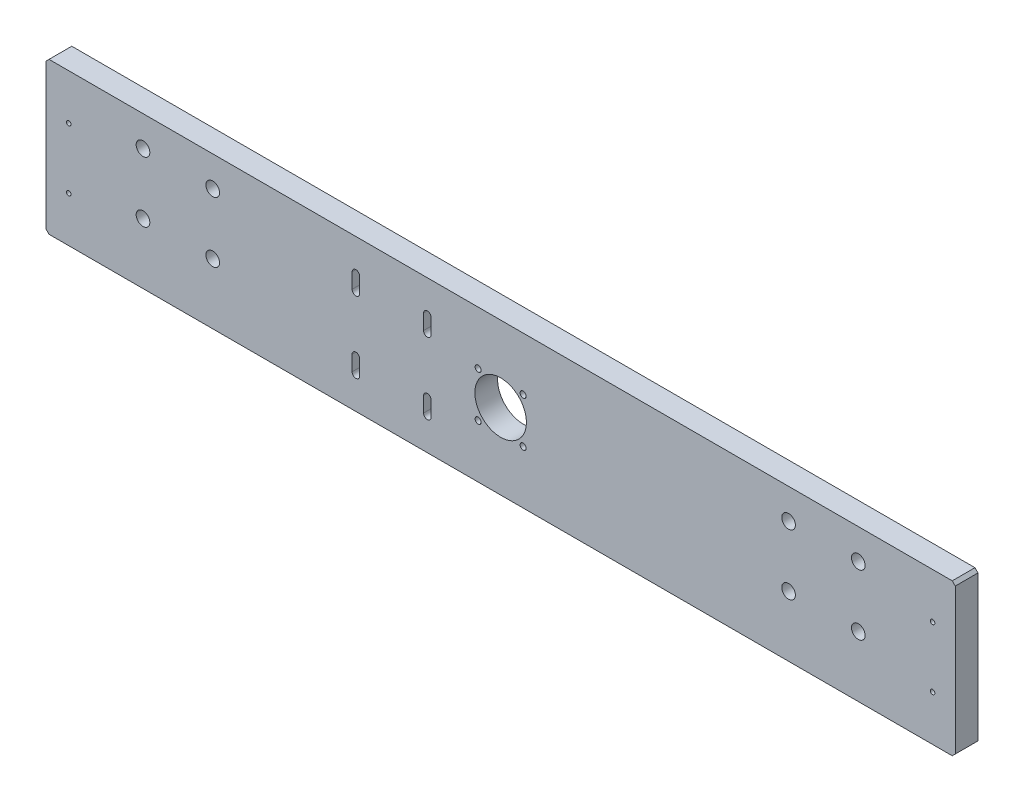
SolidWorks part; units mm, degrees
ref_plane "Piano frontale" through (0, 0, 0) normal (0, 0, 1) x (1, 0, 0)
ref_plane "Piano superiore" through (0, 0, 0) normal (0, 1, 0) x (1, 0, 0)
ref_plane "Piano destro" through (0, 0, 0) normal (1, 0, 0) x (0, 0, -1)
sketch "Schizzo1" plane through (0, 0, 0) normal (0, 0, 1) x (1, 0, 0)
  line L0 (300, 100) -> (300, 0) construction
  line L1 (2, 0) -> (598, 0)
  line L2 (0, 2) -> (0, 98)
  line L3 (2, 100) -> (598, 100)
  line L4 (600, 2) -> (600, 98)
  line L5 (87, 100) -> (87, 0) construction
  line L7 (300, 50) -> (318.5099, 50) construction
  line L9 (300, 50) -> (280.51, 69.49) construction
  line L21 (0, 98) -> (2, 100)
  line L22 (2, 0) -> (0, 2)
  line L23 (598, 0) -> (600, 2)
  line L24 (598, 100) -> (600, 98)
  circle A0 centre (300, 50) radius 17
  circle A1 centre (300, 50) radius 21 construction
  circle A2 centre (314.8492, 64.8492) radius 2
  circle A3 centre (314.8492, 35.1508) radius 2
  circle A4 centre (285.1508, 35.1508) radius 2
  circle A5 centre (536, 40) radius 4.5
  circle A6 centre (536, 80) radius 4.5
  circle A7 centre (490, 40) radius 4.5
  circle A8 centre (490, 80) radius 4.5
  circle A9 centre (585, 70) radius 1.5
  circle A10 centre (585, 30) radius 1.5
  circle A11 centre (15, 30) radius 1.5
  circle A13 centre (285.1508, 64.8492) radius 2
  circle A18 centre (15, 70) radius 1.5
  circle A29 centre (110, 80) radius 4.5
  circle A30 centre (110, 40) radius 4.5
  circle A32 centre (64, 80) radius 4.5
  circle A33 centre (64, 40) radius 4.5
  point P0 (0, 0)
  point P1 (600, 100)
  point P2 (0, 100)
  point P3 (600, 0)
  point P9 (285.1508, 64.8492)
  point P13 (285.1508, 64.8492)
  dimension "D4" = 34
  dimension "D10" = 23
  dimension "D15" = 3
  dimension "D17" = 4
  dimension "D8" = 45
  dimension "D5" = 42
  dimension "D9" = 64
  dimension "D11" = 9
  dimension "D1" = 100
  dimension "D2" = 600
  dimension "D6" = 20
  dimension "D7" = 40
  dimension "D14" = 30
  dimension "D16" = 15
extrude "Boss-Extrude1" add sketch "Schizzo1" against normal blind 15
sketch "Sketch2" plane through (0, 0, 0) normal (0, -1, 0) x (1, 0, 0)
  line L0 (2, -7.5) -> (598, -7.5) construction
  line L1 (2, -15) -> (2, 0) construction
  line L2 (598, -15) -> (598, 0) construction
  line L3 (300, -15) -> (300, 0) construction
  line L4 (2, -15) -> (598, -15) construction
  line L5 (321, 0) -> (279, 0) construction
  line L6 (0, -15) -> (0, 0) construction
  point P12 (30, -7.5)
  point P15 (570, -7.5)
  dimension "D1" = 30
hole_wizard "M8 Tapped Hole1" positions "3DSketch1" profile "Sketch3" tap size "M8" standard "ISO"
sketch3d "3DSketch1"
  point P0 (30, 0, -7.5)
  point P3 (570, 0, -7.5)
sketch "Sketch3" plane through (30, 0, -7.5) normal (1, 0, 0) x (0, 0, -1)
  line L0 (0, 0) -> (0, 25.7929)
  line L1 (0, 25.7929) -> (3.4, 23.75)
  line L2 (3.4, 23.75) -> (3.4, 0)
  line L5 (3.4, 0) -> (0, 0)
  line L10 (0, 25.7929) -> (-3.4, 23.75) construction
  line L11 (0, -6.35) -> (0, 107.95) construction
  dimension "Tap Drill Dia." = 6.8
  dimension "Tap Drill Depth" = 23.75
  dimension "Drill Angle" = 118
sketch "Sketch4" plane through (0, 0, -15) normal (0, 0, -1) x (-1, 0, 0)
  line L0 (0, 50) -> (-300, 50) construction
  line L1 (0, 2) -> (0, 98) construction
  line L2 (-251.6354, 100) -> (-251.6354, 0) construction
  line L3 (-2, 100) -> (-598, 100) construction
  line L4 (-2, 0) -> (-598, 0) construction
  line L5 (-204.4954, 100) -> (-204.4954, 0) construction
  line L6 (-251.6354, 68.57) -> (-251.6354, 78.57) construction
  line L7 (-254.1354, 68.57) -> (-254.1354, 78.57)
  line L8 (-249.1354, 68.57) -> (-249.1354, 78.57)
  line L9 (-204.4954, 68.57) -> (-204.4954, 78.57) construction
  line L10 (-206.9954, 68.57) -> (-206.9954, 78.57)
  line L11 (-201.9954, 68.57) -> (-201.9954, 78.57)
  line L12 (-251.6354, 21.43) -> (-251.6354, 31.43) construction
  line L13 (-254.1354, 21.43) -> (-254.1354, 31.43)
  line L14 (-249.1354, 21.43) -> (-249.1354, 31.43)
  line L15 (-204.4954, 21.43) -> (-204.4954, 31.43) construction
  line L16 (-206.9954, 21.43) -> (-206.9954, 31.43)
  line L17 (-201.9954, 21.43) -> (-201.9954, 31.43)
  arc A0 (-254.1354, 68.57) -> (-249.1354, 68.57) centre (-251.6354, 68.57) ccw
  arc A1 (-249.1354, 78.57) -> (-254.1354, 78.57) centre (-251.6354, 78.57) ccw
  arc A2 (-206.9954, 68.57) -> (-201.9954, 68.57) centre (-204.4954, 68.57) ccw
  arc A3 (-201.9954, 78.57) -> (-206.9954, 78.57) centre (-204.4954, 78.57) ccw
  arc A4 (-254.1354, 21.43) -> (-249.1354, 21.43) centre (-251.6354, 21.43) ccw
  arc A5 (-249.1354, 31.43) -> (-254.1354, 31.43) centre (-251.6354, 31.43) ccw
  arc A6 (-206.9954, 21.43) -> (-201.9954, 21.43) centre (-204.4954, 21.43) ccw
  arc A7 (-201.9954, 31.43) -> (-206.9954, 31.43) centre (-204.4954, 31.43) ccw
  point P0 (-251.6354, 73.57)
  point P1 (-204.4954, 73.57)
  point P2 (-204.4954, 26.43)
  point P3 (-251.6354, 26.43)
  point P19 (-251.6354, 73.57)
  point P26 (-204.4954, 73.57)
  point P32 (-251.6354, 26.43)
  point P39 (-204.4954, 26.43)
  dimension "D1" = 47.14
  dimension "D2" = 47.14
  dimension "D3" = 5
  dimension "D4" = 10
extrude "Cut-Extrude1" cut sketch "Sketch4" against normal through all
